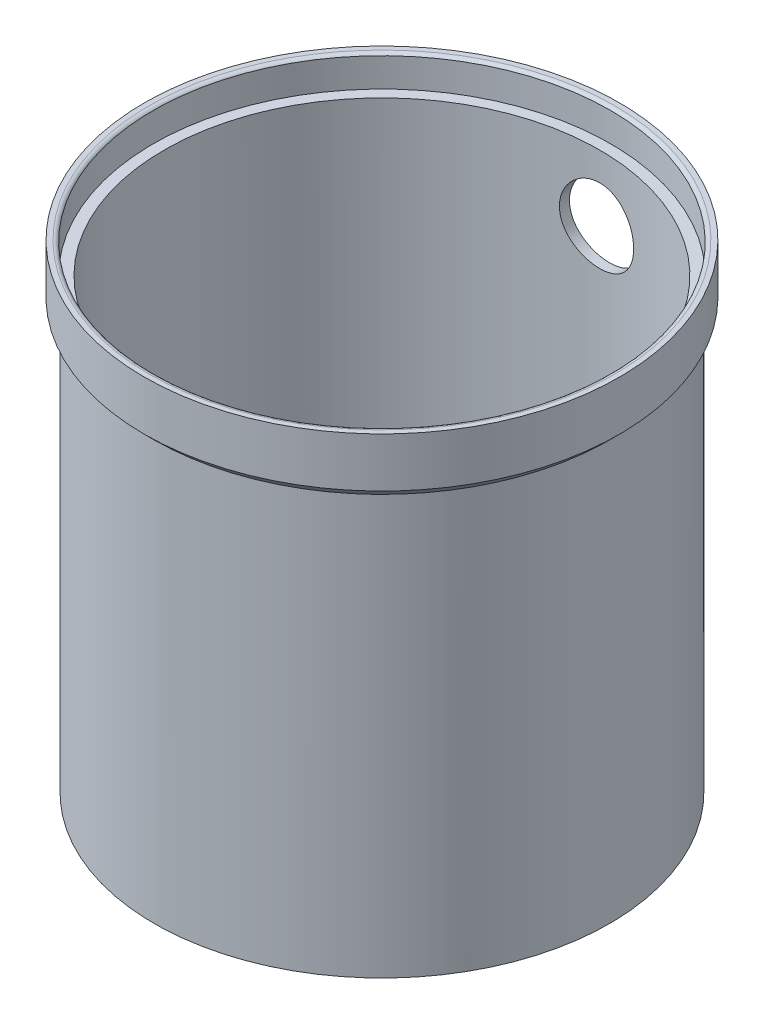
SolidWorks part; units mm, degrees
ref_plane "Front Plane" through (0, 0, 0) normal (0, 0, 1) x (1, 0, 0)
ref_plane "Top Plane" through (0, 0, 0) normal (0, 1, 0) x (1, 0, 0)
ref_plane "Right Plane" through (0, 0, 0) normal (1, 0, 0) x (0, 0, -1)
sketch "Sketch1" plane through (0, 0, 0) normal (0, 1, 0) x (1, 0, 0)
  circle A0 centre (0, 0) radius 36.8
  circle A1 centre (0, 0) radius 35.2
  dimension "D1" = 73.6
  dimension "D2" = 1.6
extrude "Boss-Extrude1" add sketch "Sketch1" along normal blind 70
sketch "Sketch2" plane through (0, 70, 0) normal (0, 1, 0) x (1, 0, 0)
  circle A1 centre (0, 0) radius 36.8
  circle A2 centre (0, 0) radius 36.8
  circle A3 centre (0, 0) radius 38.4
  dimension "D1" = 0
  dimension "D2" = 1.6
extrude "Boss-Extrude2" add sketch "Sketch2" along normal blind 5 and the other way blind 5
chamfer "Chamfer1" distance 2 angle 45 1 edges at (0, 65, 38.4)
fillet "Fillet1" radius 0.8 1 edges at (0, 75, 36.8)
sketch "Sketch3" plane through (0, 0, 0) normal (0, -1, 0) x (1, 0, 0)
  circle A0 centre (0, 0) radius 36.8 construction
  circle A1 centre (0, 0) radius 36.8
  circle A2 centre (0, 0) radius 36.2
  dimension "D1" = 0.6
extrude "Boss-Extrude3" add sketch "Sketch3" along normal blind 2.3
chamfer "Chamfer2" distance 1 angle 45 1 edges at (0, 0, 35.2)
sketch "Sketch5" plane through (0, 70, 0) normal (0, 1, 0) x (1, 0, 0)
  circle A2 centre (0, 0) radius 36.95
  circle A3 centre (0, 0) radius 36.95
  dimension "D1" = 0.15
extrude "Cut-Extrude1" cut sketch "Sketch5" along normal blind 10
ref_plane "Plane1" through (0, 0, -36.8) normal (0, 0, -1) x (-1, 0, 0)
sketch "Sketch6" plane through (0, 0, -36.8) normal (0, 0, -1) x (-1, 0, 0)
  line L0 (0, 65.4) -> (0, 47.592) construction
  line L1 (36.8, 65.4) -> (-36.8, 65.4) construction
  circle A0 centre (0, 59.4) radius 6
  dimension "D1" = 12
  dimension "D2" = 6
extrude "Cut-Extrude2" cut sketch "Sketch6" against normal blind 10
